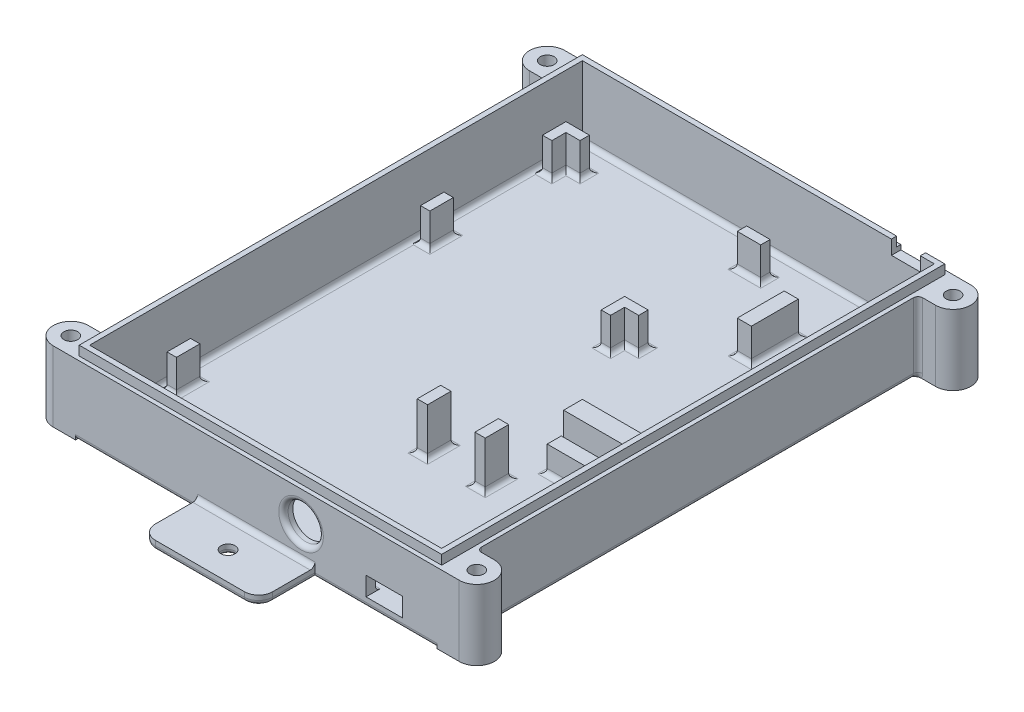
SolidWorks part; units mm, degrees
ref_plane "Front" through (0, 0, 0) normal (0, 0, 1) x (1, 0, 0)
ref_plane "Top" through (0, 0, 0) normal (0, 1, 0) x (1, 0, 0)
ref_plane "Right" through (0, 0, 0) normal (1, 0, 0) x (0, 0, -1)
sketch "Sketch1" plane through (0, 0, 0) normal (0, 1, 0) x (1, 0, 0)
  line L0 (-39.5, 0) -> (39.5, 0) construction
  line L1 (-39.5, -54.5) -> (39.5, -54.5)
  line L2 (-39.5, -54.5) -> (-39.5, 54.5)
  line L3 (-39.5, 54.5) -> (39.5, 54.5)
  line L4 (39.5, -54.5) -> (39.5, 54.5)
  line L5 (-39.5, -54.5) -> (39.5, 54.5) construction
  line L6 (-39.5, 54.5) -> (39.5, -54.5) construction
  line L7 (-12.5, 54.5) -> (12.5, 54.5)
  line L8 (-12.5, 54.5) -> (-12.5, 63.5)
  line L9 (-9.5, 66.5) -> (9.5, 66.5)
  line L10 (12.5, 54.5) -> (12.5, 63.5)
  line L11 (12.5, -54.5) -> (12.5, -63.5)
  line L12 (-9.5, -66.5) -> (9.5, -66.5)
  line L13 (-12.5, -54.5) -> (-12.5, -63.5)
  line L14 (39.5, 54.5) -> (64.4195, 54.5) construction
  line L15 (0, 60.5) -> (0, 0) construction
  line L16 (0, 0) -> (59.9172, 0) construction
  line L17 (43, 54.5) -> (39.5, 54.5)
  line L18 (43, 47.5) -> (39.5, 47.5)
  line L19 (-43, 54.5) -> (-39.5, 54.5)
  line L20 (-43, 47.5) -> (-39.5, 47.5)
  line L21 (-43, -54.5) -> (-39.5, -54.5)
  line L22 (-43, -47.5) -> (-39.5, -47.5)
  line L23 (43, -54.5) -> (39.5, -54.5)
  line L24 (43, -47.5) -> (39.5, -47.5)
  arc A0 (9.5, 66.5) -> (12.5, 63.5) centre (9.5, 63.5) cw
  arc A1 (-12.5, 63.5) -> (-9.5, 66.5) centre (-9.5, 63.5) cw
  circle A2 centre (0, 60.5) radius 1.5
  arc A3 (9.5, -66.5) -> (12.5, -63.5) centre (9.5, -63.5) ccw
  circle A4 centre (0, -60.5) radius 1.5
  arc A5 (-12.5, -63.5) -> (-9.5, -66.5) centre (-9.5, -63.5) ccw
  arc A6 (43, 47.5) -> (43, 54.5) centre (43, 51) ccw
  arc A7 (-43, 47.5) -> (-43, 54.5) centre (-43, 51) cw
  arc A8 (-43, -47.5) -> (-43, -54.5) centre (-43, -51) ccw
  arc A9 (43, -47.5) -> (43, -54.5) centre (43, -51) cw
  point P0 (0, 0)
  point P10 (0, 66.5)
  point P13 (12.5, 66.5)
  point P16 (-12.5, 66.5)
  point P22 (0, 0)
  dimension "D5" = 3
  dimension "D6" = 3
  dimension "D9" = 7
  dimension "D1" = 109
  dimension "D2" = 79
  dimension "D3" = 25
  dimension "D4" = 12
  dimension "D7" = 6
extrude "Boss-Extrude1" add sketch "Sketch1" along normal blind 2 contours A1 L8 L3 L10 A0 L9 A2 | L1 L4 L3 L2 | L13 A5 L12 A3 L11 L1 A4 region at (0, 0, 0) region at (0, 0, 54.7773) region at (-12.2227, 0, -59)
sketch "Sketch3" plane through (0, 2, 0) normal (0, 1, 0) x (1, 0, 0)
  line L0 (0, 0) -> (0, -83.3286) construction
  line L1 (-37.5, -52.5) -> (37.5, -52.5)
  line L2 (-37.5, -52.5) -> (-37.5, 52.5)
  line L3 (-37.5, 52.5) -> (37.5, 52.5)
  line L4 (37.5, -52.5) -> (37.5, 52.5)
  line L5 (-37.5, -52.5) -> (37.5, 52.5) construction
  line L6 (-37.5, 52.5) -> (37.5, -52.5) construction
  line L7 (-39.5, -54.5) -> (39.5, -54.5)
  line L8 (-39.5, -54.5) -> (-39.5, 54.5)
  line L9 (-39.5, 54.5) -> (39.5, 54.5)
  line L10 (39.5, -54.5) -> (39.5, 54.5)
  line L11 (-39.5, -54.5) -> (39.5, 54.5) construction
  line L12 (-39.5, 54.5) -> (39.5, -54.5) construction
  line L13 (0, 0) -> (62.6856, 0) construction
  point P0 (0, 0)
  point P6 (0, 0)
  dimension "D1" = 75
  dimension "D2" = 105
extrude "Boss-Extrude3" add sketch "Sketch3" along normal blind 15
sketch "Sketch4" plane through (0, 2, 0) normal (0, 1, 0) x (1, 0, 0)
  line L0 (-37.5, -52.5) -> (37.5, -52.5) construction
  line L1 (2.3, -17.5) -> (4.5, -17.5)
  line L2 (2.3, -17.5) -> (2.3, -22.5)
  line L3 (2.3, -22.5) -> (4.5, -22.5)
  line L4 (4.5, -17.5) -> (4.5, -22.5)
  line L5 (37.5, -52.5) -> (37.5, 52.5) construction
  line L7 (14.6, -17.5) -> (16.8, -17.5)
  line L8 (14.6, -17.5) -> (14.6, -22.5)
  line L9 (14.6, -22.5) -> (16.8, -22.5)
  line L10 (16.8, -17.5) -> (16.8, -22.5)
  dimension "D1" = 30
  dimension "D2" = 33
  dimension "D3" = 5
  dimension "D4" = 2.2
  dimension "D5" = 2.2
  dimension "D6" = 5
  dimension "D7" = 10.1
extrude "Boss-Extrude4" add sketch "Sketch4" along normal blind 10
sketch "Sketch5" plane through (0, 2, 0) normal (0, 1, 0) x (1, 0, 0)
  line L0 (-37.5, -52.5) -> (37.5, -52.5) construction
  line L1 (20, -9.5) -> (35, -9.5)
  line L2 (20, -9.5) -> (20, -12.5)
  line L3 (20, -12.5) -> (35, -12.5)
  line L4 (35, -9.5) -> (35, -12.5)
  line L5 (37.5, -52.5) -> (37.5, 52.5) construction
  dimension "D1" = 15
  dimension "D2" = 3
  dimension "D3" = 40
  dimension "D4" = 2.5
extrude "Boss-Extrude5" add sketch "Sketch5" along normal blind 5.5
sketch "Sketch6" plane through (0, 2, 0) normal (0, 1, 0) x (1, 0, 0)
  line L0 (-31, 45.5) -> (-34, 45.5)
  line L1 (-34, 45.5) -> (-34, 42.5)
  line L2 (-34, 42.5) -> (-36, 42.5)
  line L3 (-36, 42.5) -> (-36, 47.5)
  line L4 (-36, 47.5) -> (-31, 47.5)
  line L5 (-31, 47.5) -> (-31, 45.5)
  line L6 (-37.5, 52.5) -> (-37.5, -52.5) construction
  line L7 (37.5, 52.5) -> (-37.5, 52.5) construction
  line L8 (2.5, 16.5) -> (2.5, 21.5)
  line L9 (2.5, 21.5) -> (7.5, 21.5)
  line L10 (-37.5, -52.5) -> (37.5, -52.5) construction
  line L11 (37.5, -52.5) -> (37.5, 52.5) construction
  line L12 (2.5, 16.5) -> (4.5, 16.5)
  line L13 (4.5, 16.5) -> (4.5, 19.5)
  line L14 (4.5, 19.5) -> (7.5, 19.5)
  line L15 (7.5, 19.5) -> (7.5, 21.5)
  line L16 (-36, -32.5) -> (-34, -32.5)
  line L17 (-36, -32.5) -> (-36, -37.5)
  line L18 (-36, -37.5) -> (-34, -37.5)
  line L19 (-34, -32.5) -> (-34, -37.5)
  line L20 (-36, 21.5) -> (-34, 21.5)
  line L21 (-36, 21.5) -> (-36, 16.5)
  line L22 (-36, 16.5) -> (-34, 16.5)
  line L23 (-34, 21.5) -> (-34, 16.5)
  line L24 (2.5, 47.5) -> (7.5, 47.5)
  line L25 (2.5, 47.5) -> (2.5, 45.5)
  line L26 (2.5, 45.5) -> (7.5, 45.5)
  line L27 (7.5, 47.5) -> (7.5, 45.5)
  dimension "D1" = 3.5
  dimension "D2" = 7
  dimension "D3" = 2
  dimension "D4" = 2
  dimension "D5" = 5
  dimension "D6" = 5
  dimension "D7" = 35
  dimension "D8" = 2
  dimension "D9" = 2
  dimension "D10" = 5
  dimension "D11" = 5
  dimension "D12" = 31
  dimension "D13" = 5
  dimension "D14" = 2
  dimension "D15" = 15
  dimension "D16" = 1.5
  dimension "D17" = 5
  dimension "D18" = 2
  dimension "D19" = 1.5
  dimension "D20" = 2
  dimension "D21" = 5
extrude "Boss-Extrude6" add sketch "Sketch6" along normal blind 7
sketch "Sketch7" plane through (0, 0, 54.5) normal (0, 0, 1) x (1, 0, 0)
  line L0 (39.5, 2) -> (27.3, 2) construction
  line L1 (39.5, 17) -> (39.5, 0) construction
  line L2 (23.4, 2) -> (31.2, 2)
  line L3 (12.5, 0) -> (39.5, 0) construction
  line L4 (31.2, 2) -> (31.2, 6)
  line L5 (31.2, 6) -> (23.4, 6)
  line L6 (23.4, 6) -> (23.4, 2)
  line L7 (39.5, 2) -> (9.55, 2) construction
  line L8 (9.55, 2) -> (9.55, 15) construction
  line L9 (9.55, 8.5) -> (7.9037, 8.5) construction
  circle A0 centre (9.55, 8.5) radius 3.75
  point P6 (27.3, 2)
  dimension "D6" = 7.5
  dimension "D1" = 12.2
  dimension "D2" = 7.8
  dimension "D3" = 2
  dimension "D4" = 4
  dimension "D5" = 29.95
  dimension "D7" = 13
extrude "Cut-Extrude1" cut sketch "Sketch7" against normal blind 7
sketch "Sketch8" plane through (0, 17, 0) normal (0, 1, 0) x (1, 0, 0)
  line L1 (-38.61, -53.61) -> (38.61, -53.61)
  line L2 (-38.61, -53.61) -> (-38.61, 53.61)
  line L3 (-38.61, 53.61) -> (38.61, 53.61)
  line L4 (38.61, -53.61) -> (38.61, 53.61)
  line L5 (-38.61, -53.61) -> (38.61, 53.61) construction
  line L6 (-38.61, 53.61) -> (38.61, -53.61) construction
  line L7 (-39.5, 54.5) -> (39.5, 54.5)
  line L8 (-39.5, 54.5) -> (-39.5, -54.5)
  line L9 (-39.5, -54.5) -> (39.5, -54.5)
  line L10 (39.5, 54.5) -> (39.5, -54.5)
  line L11 (-39.5, 54.5) -> (39.5, -54.5) construction
  line L12 (-39.5, -54.5) -> (39.5, 54.5) construction
  point P0 (0, 0)
  point P6 (0, 0)
  dimension "D1" = 0.89
  dimension "D2" = 0.89
extrude "Cut-Extrude2" cut sketch "Sketch8" against normal blind 2
sketch "Sketch9" plane through (0, 2, 0) normal (0, 1, 0) x (1, 0, 0)
  line L0 (31.2, -52.5) -> (37.5, -52.5) construction
  line L1 (20, -5) -> (35, -5)
  line L2 (20, -5) -> (20, -9)
  line L3 (20, -9) -> (35, -9)
  line L4 (35, -5) -> (35, -9)
  line L5 (20, -9.5) -> (20, -12.5) construction
  line L6 (35, -12.5) -> (35, -9.5) construction
  dimension "D1" = 43.5
  dimension "D2" = 4
extrude "Boss-Extrude7" add sketch "Sketch9" along normal blind 10
sketch "Sketch10" plane through (0, 2, 0) normal (0, 1, 0) x (1, 0, 0)
  line L0 (37.5, -52.5) -> (37.5, 52.5) construction
  line L1 (18.5, 39.5) -> (21.5, 39.5)
  line L2 (18.5, 39.5) -> (18.5, 29.5)
  line L3 (18.5, 29.5) -> (21.5, 29.5)
  line L4 (21.5, 39.5) -> (21.5, 29.5)
  line L5 (37.5, 52.5) -> (-37.5, 52.5) construction
  dimension "D1" = 16
  dimension "D2" = 3
  dimension "D3" = 13
  dimension "D4" = 10
extrude "Boss-Extrude8" add sketch "Sketch10" along normal blind 7
sketch "Sketch11" plane through (0, 0, -52.5) normal (0, 0, 1) x (1, 0, 0)
  line L0 (37.5, 17) -> (-37.5, 17) construction
  line L1 (34.5, 17) -> (28.35, 17)
  line L2 (34.5, 17) -> (34.5, 14)
  line L3 (34.5, 14) -> (28.35, 14)
  line L4 (28.35, 17) -> (28.35, 14)
  line L5 (37.5, 17) -> (37.5, 2) construction
  dimension "D1" = 6.15
  dimension "D2" = 3
  dimension "D3" = 3
extrude "Cut-Extrude3" cut sketch "Sketch11" against normal blind 7
fillet "Fillet1" radius 1 47 edges at (21.5, 2, -34.5) (20, 2, -39.5) (18.5, 2, -34.5) (20, 2, -29.5) (35, 2, 7) (27.5, 2, 5) (20, 2, 7) (6, 2, -19.5) (7.5, 2, -20.5) (5, 2, -21.5) (2.5, 2, -19) (3.5, 2, -16.5) (4.5, 2, -18) (-36, 2, -45) (-35, 2, -42.5) (-34, 2, -44) (-32.5, 2, -45.5) (-31, 2, -46.5) (-33.5, 2, -47.5) (35, 2, 11) (20, 2, 11) (27.5, 2, 12.5) (16.8, 2, 20) (15.7, 2, 17.5) (14.6, 2, 20) (15.7, 2, 22.5) (4.5, 2, 20) (3.4, 2, 17.5) (2.3, 2, 20) (3.4, 2, 22.5) (-37.5, 2, 0) (0, 2, -52.5) (37.5, 2, 0) (34.35, 2, 52.5) (-7.05, 2, 52.5) (-36, 2, 35) (-35, 2, 37.5) (-35, 2, 32.5) (-34, 2, 35) (-36, 2, -19) (-35, 2, -21.5) (-35, 2, -16.5) (-34, 2, -19) (2.5, 2, -46.5) (5, 2, -45.5) (7.5, 2, -46.5) (5, 2, -47.5)
fillet "Fillet2" radius 1 23 edges at (0, 0, 62) (-12.5, 0, -59) (-26, 0, -54.5) (-39.5, 0, 0) (-26, 0, 54.5) (-12.5, 0, 59) (-11.6213, 0, 65.6213) (0, 0, 66.5) (11.6213, 0, 65.6213) (12.5, 0, 59) (26, 0, 54.5) (39.5, 0, 0) (26, 0, -54.5) (12.5, 0, -59) (11.6213, 0, -65.6213) (0, 0, -66.5) (-11.6213, 0, -65.6213) (0, 0, -59) (13.3, 8.5, 54.5) (-39.5, 7.5, -54.5) (39.5, 7.5, -54.5) (39.5, 7.5, 54.5) (-39.5, 7.5, 54.5)
fillet "Fillet3" radius 1 2 edges at (0, 2, 54.5) (0, 2, -54.5)
sketch "Sketch12" plane through (0, 2, 0) normal (0, 1, 0) x (1, 0, 0)
  line L0 (5.5, -23.5) -> (13.6, -23.5) construction
  line L1 (9.55, -23.5) -> (9.55, -51.5) construction
  line L2 (-36.5, -51.5) -> (23.4, -51.5) construction
  line L3 (39.5, -53.5) -> (39.5, 53.5) construction
  dimension "D1" = 29.95
sketch "Sketch14" plane through (0, 0, 0) normal (0, -1, 0) x (1, 0, 0)
  line L0 (34.6422, 54.5) -> (49.6778, 54.5) construction
  line L1 (12.5, 54.5) -> (38.5, 54.5) construction
  line L2 (0, 0) -> (10.7867, 0) construction
  line L3 (0, 0) -> (0, 12.6069) construction
  line L4 (39.5, 53.5) -> (39.5, -53.5) construction
  line L5 (43.25, 54.5) -> (38.5, 54.5)
  line L6 (43.25, 47) -> (38.5, 47)
  line L7 (38.5, -53.5) -> (38.5, 53.5) construction
  line L8 (-43.25, 47) -> (-38.5, 47)
  line L9 (-43.25, 54.5) -> (-38.5, 54.5)
  line L10 (43.25, -54.5) -> (38.5, -54.5)
  line L11 (43.25, -47) -> (38.5, -47)
  line L12 (-43.25, -54.5) -> (-38.5, -54.5)
  line L13 (-43.25, -47) -> (-38.5, -47)
  line L14 (38.5, 54.5) -> (38.5, 47)
  line L15 (-38.5, 54.5) -> (-38.5, 47)
  line L16 (-38.5, -47) -> (-38.5, -54.5)
  line L17 (38.5, -47) -> (38.5, -54.5)
  arc A0 (43.25, 47) -> (43.25, 54.5) centre (43.25, 50.75) ccw
  arc A1 (-43.25, 47) -> (-43.25, 54.5) centre (-43.25, 50.75) cw
  arc A2 (43.25, -47) -> (43.25, -54.5) centre (43.25, -50.75) cw
  arc A3 (-43.25, -47) -> (-43.25, -54.5) centre (-43.25, -50.75) ccw
  dimension "D1" = 7.5
extrude "Boss-Extrude10" add sketch "Sketch14" against normal blind 15
sketch "Sketch15" plane through (0, 0, 0) normal (0, -1, 0) x (1, 0, 0)
  line L0 (0, 0) -> (0, 12.2549) construction
  line L1 (0, 0) -> (8.5513, 0) construction
  circle A0 centre (43.25, 50.75) radius 2.75
  circle A1 centre (-43.25, 50.75) radius 2.75
  circle A2 centre (-43.25, -50.75) radius 2.75
  circle A3 centre (43.25, -50.75) radius 2.75
  dimension "D1" = 5.5
extrude "Cut-Extrude4" cut sketch "Sketch15" against normal blind 3
sketch "Sketch17" plane through (0, 3, 0) normal (0, -1, 0) x (1, 0, 0)
  line L0 (0, 0) -> (6.4497, 0) construction
  line L1 (0, 0) -> (0, 9.9664) construction
  circle A0 centre (43.25, 50.75) radius 1.475
  circle A1 centre (43.25, -50.75) radius 1.475
  circle A2 centre (-43.25, 50.75) radius 1.475
  circle A3 centre (-43.25, -50.75) radius 1.475
  dimension "D1" = 2.95
extrude "Cut-Extrude5" cut sketch "Sketch17" against normal through all
fillet "Fillet5" radius 1 8 edges at (-39.5, 8, 47) (-39.5, 8, -47) (39.5, 8, -47) (39.5, 8, 47) (-39.2071, 0.2929, 47) (-39.2071, 0.2929, -47) (39.2071, 0.2929, -47) (39.2071, 0.2929, 47)
